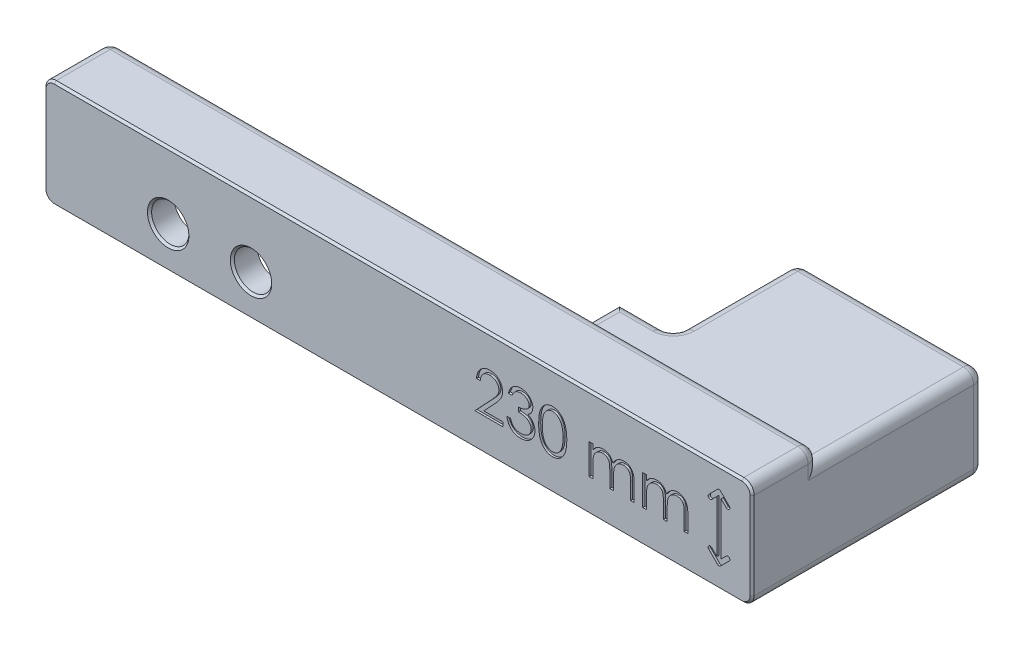
SolidWorks part; units mm, degrees
ref_plane "Front Plane" through (0, 0, 0) normal (0, 0, 1) x (1, 0, 0)
ref_plane "Top Plane" through (0, 0, 0) normal (0, 1, 0) x (1, 0, 0)
ref_plane "Right Plane" through (0, 0, 0) normal (1, 0, 0) x (0, 0, -1)
sketch "main_features_sketch" plane through (0, 0, 0) normal (0, 0, 1) x (1, 0, 0)
  line L0 (24, 290) -> (0, 290) construction
  line L1 (0, 300) -> (0, 0) construction
  line L2 (107, 300) -> (107, 0) construction
  line L3 (0, 300) -> (107, 300)
  line L4 (0, 300) -> (0, 280)
  line L5 (0, 280) -> (107, 280)
  line L6 (107, 300) -> (107, 280)
  line L7 (0, 280) -> (-6, 280)
  line L8 (-6, 280) -> (-6, 306)
  line L9 (-6, 306) -> (113, 306)
  line L10 (113, 306) -> (113, 280)
  line L11 (113, 280) -> (107, 280)
  line L12 (0, 300) -> (0, 306) construction
  line L13 (113, 280) -> (165, 280)
  line L14 (165, 280) -> (165, 302.6)
  line L15 (165, 302.6) -> (113, 302.6)
  line L17 (120, 280) -> (120, 302.6)
  line L18 (117, 615.8017) -> (117, -1840.1983) construction
  line L19 (113, 306) -> (165, 306)
  line L20 (165, 306) -> (165, 302.6)
  line L21 (113, 302.6) -> (107, 302.6)
  line L23 (107, 302.6) -> (107, 300)
  circle A0 centre (24, 290) radius 3.1
  circle A1 centre (44, 290) radius 3.1
  line M24 (67.2, 300) -> (1, 300)
  line M25 (1, 300) -> (1, 0)
  line M27 (67.2, 0) -> (67.2, 300)
  circle M35 centre (24, 290) radius 4.5
  circle M39 centre (44, 290) radius 4.5
  dimension "D1" = 6.2
  dimension "D2" = 6
  dimension "D3" = 45
  dimension "D4" = 3
  dimension "D5" = 22.6
extrude "base" add sketch "main_features_sketch" along normal blind 6 contours L5 M25 M27 M24 M35 M39 | L11 L10 L9 L8 L7 L4 L3 L6 M24 | L6 L3 L5 M27 | L20 L19 L10 L15 | L17 L13 L14 L15 | L13 L17 L15 L10 | L4 L5 L3 M25 | L21 L23 L6 L11 L10 region at (44.1386, 301.1262, 0) region at (0.5, 290, 0) region at (34.1106, 290, 0) region at (87.1, 290, 0) region at (110, 291.3, 0) region at (139, 304.3, 0) region at (116.5, 291.3, 0) region at (142.5, 291.3, 0)
extrude "ledge" add sketch "main_features_sketch<3>" against normal blind 10 contours L11 L10 L9 L8 L7 L4 L3 L6 M24 | L20 L19 L10 L15 region at (44.1386, 301.1262, 0) region at (139, 304.3, 0)
sketch "main_features_sketch<3>" plane through (0, 0, 0) normal (0, 0, 1) x (1, 0, 0) same geometry as "main_features_sketch"
extrude "Boss-Extrude3" add sketch "main_features_sketch<4>" against normal blind 20 contours L21 L23 L6 L11 L10 | L13 L17 L15 L10 region at (110, 291.3, 0) region at (116.5, 291.3, 0)
sketch "main_features_sketch<4>" plane through (0, 0, 0) normal (0, 0, 1) x (1, 0, 0) same geometry as "main_features_sketch"
extrude "Boss-Extrude4" add sketch "main_features_sketch<5>" against normal blind 50 contours L17 L13 L14 L15 region at (142.5, 291.3, 0)
sketch "main_features_sketch<5>" plane through (0, 0, 0) normal (0, 0, 1) x (1, 0, 0) same geometry as "main_features_sketch"
fillet "Fillet1" radius 2.5 20 edges at (113.5, 280, -20) (113.5, 302.6, -20) (142.5, 280, -50) (165, 291.3, -50) (142.5, 302.6, -50) (120, 291.3, -50) (165, 304.3, -10) (79.5, 306, -10) (-6, 293, -10) (0, 280, -5) (120, 291.3, -20) (120, 302.6, -35) (107, 302.6, -15) (120, 280, -35) (107, 280, -10) (-6, 280, -2) (-6, 306, -2) (165, 306, -2) (165, 302.6, -30) (165, 280, -22)
chamfer "Chamfer1" distance 0.5 angle 45 10 edges at (48.5, 290, 6) (28.5, 290, 6) (-5.2678, 305.2678, 6) (79.5, 306, 6) (164.2678, 305.2678, 6) (165, 293, 6) (164.2678, 280.7322, 6) (79.5, 280, 6) (-5.2678, 280.7322, 6) (-6, 293, 6)
sketch "Sketch3" plane through (0, 0, 6) normal (0, 0, 1) x (1, 0, 0)
  line L1 (157, 300.5) -> (157, 285.5)
  line L2 (157, 285.5) -> (154.8787, 287.6213)
  line L3 (157, 285.5) -> (159.1213, 287.6213)
  line L4 (157, 300.5) -> (154.8787, 298.3787)
  line L5 (157, 300.5) -> (159.1213, 298.3787)
  line L6 (165, 293) -> (157, 293) construction
  line L7 (165, 303.5) -> (165, 282.5) construction
  line L8 (156.6464, 300.8536) -> (154.5251, 298.7322)
  line L9 (156.5, 300.5) -> (156.5, 285.5)
  line L10 (156.6464, 300.1464) -> (158.7678, 298.0251)
  line L11 (157.3536, 285.1464) -> (159.4749, 287.2678)
  line L12 (157.3536, 285.8536) -> (155.2322, 287.9749)
  line L13 (157.3536, 300.1464) -> (155.2322, 298.0251)
  line L14 (157.5, 300.5) -> (157.5, 285.5)
  line L15 (157.3536, 300.8536) -> (159.4749, 298.7322)
  line L16 (156.6464, 285.8536) -> (158.7678, 287.9749)
  line L17 (156.6464, 285.1464) -> (154.5251, 287.2678)
  arc A0 (156.6464, 300.8536) -> (157.3536, 300.1464) centre (157, 300.5) cw
  arc A1 (154.5251, 298.7322) -> (155.2322, 298.0251) centre (154.8787, 298.3787) ccw
  arc A2 (156.5, 300.5) -> (157.5, 300.5) centre (157, 300.5) cw
  arc A3 (156.5, 285.5) -> (157.5, 285.5) centre (157, 285.5) ccw
  arc A4 (156.6464, 300.1464) -> (157.3536, 300.8536) centre (157, 300.5) cw
  arc A5 (158.7678, 298.0251) -> (159.4749, 298.7322) centre (159.1213, 298.3787) ccw
  arc A6 (157.3536, 285.1464) -> (156.6464, 285.8536) centre (157, 285.5) cw
  arc A7 (159.4749, 287.2678) -> (158.7678, 287.9749) centre (159.1213, 287.6213) ccw
  arc A8 (157.3536, 285.8536) -> (156.6464, 285.1464) centre (157, 285.5) cw
  arc A9 (155.2322, 287.9749) -> (154.5251, 287.2678) centre (154.8787, 287.6213) ccw
  dimension "D1" = 15
  dimension "D2" = 3
  dimension "D3" = 8
  dimension "D4" = 0.5
  dimension "D5" = 0.5
extrude "Cut-Extrude1" cut sketch "Sketch3" against normal blind 0.5 contours L17 A9 L12 A8 | L16 A7 L11 A6 | L14 A3 L9 A2 | L15 A5 L10 A4 | L8 A1 L13 A0
sketch "Sketch4" plane through (0, 0, 6) normal (0, 0, 1) x (1, 0, 0)
  line L0 (97.6833, 288) -> (165, 288) construction
  line L1 (165, 303.5) -> (165, 282.5) construction
  text T0 "230 mm" font "Century Gothic" height 10
  point P10 (165, 293)
  dimension "D1" = 5
extrude "Cut-Extrude2" cut sketch "Sketch4" against normal blind 0.5
